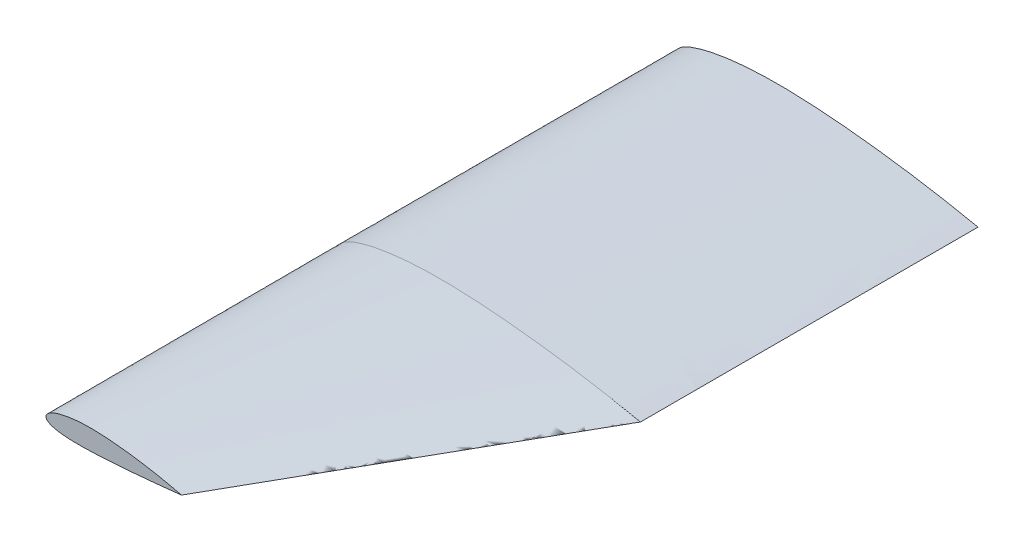
SolidWorks part; units mm, degrees
ref_plane "Front Plane" through (0, 0, 0) normal (0, 0, 1) x (1, 0, 0)
ref_plane "Top Plane" through (0, 0, 0) normal (0, 1, 0) x (1, 0, 0)
ref_plane "Right Plane" through (0, 0, 0) normal (1, 0, 0) x (0, 0, -1)
curve "Airfoil_curve"
  spline degree 3 poles (411.7804, -0.0098, 0) (412.0545, -0.0037, 0) (411.7837, 0.039, 0) (411.5616, 0.0985, 0) (411.0133, 0.2083, 0) (410.3302, 0.3565, 0) (409.4198, 0.5493, 0) (408.3206, 0.7814, 0) (407.02, 1.0557, 0) (405.5236, 1.3688, 0) (403.8317, 1.7216, 0) (401.9459, 2.1114, 0) (399.8683, 2.5387, 0) (397.6004, 3.0012, 0) (395.1447, 3.4977, 0) (392.5032, 4.0277, 0) (389.6784, 4.588, 0) (386.6731, 5.1782, 0) (383.49, 5.7963, 0) (380.1322, 6.4415, 0) (376.6026, 7.1106, 0) (372.9048, 7.8026, 0) (369.0422, 8.5155, 0) (365.0185, 9.2477, 0) (360.8375, 9.9974, 0) (356.5033, 10.7622, 0) (352.0198, 11.5401, 0) (347.3916, 12.3302, 0) (342.6227, 13.1295, 0) (337.7182, 13.9369, 0) (332.6823, 14.7493, 0) (327.5203, 15.5662, 0) (322.2368, 16.3844, 0) (316.8373, 17.2029, 0) (311.3268, 18.0191, 0) (305.7109, 18.8317, 0) (299.9947, 19.6388, 0) (294.184, 20.4376, 0) (288.2845, 21.2273, 0) (282.3019, 22.0053, 0) (276.2423, 22.7702, 0) (270.1111, 23.5198, 0) (263.9148, 24.2525, 0) (257.6594, 24.9668, 0) (251.3511, 25.6606, 0) (244.9963, 26.3314, 0) (238.6009, 26.9786, 0) (232.1717, 27.6004, 0) (225.7146, 28.1938, 0) (219.2366, 28.7588, 0) (212.7437, 29.2926, 0) (206.2427, 29.7945, 0) (199.7399, 30.2623, 0) (193.242, 30.6937, 0) (186.7555, 31.0897, 0) (180.2868, 31.4464, 0) (173.8427, 31.7639, 0) (167.4194, 32.0406, 0) (161.0164, 32.2752, 0) (154.6398, 32.4509, 0) (148.3063, 32.5705, 0) (142.0295, 32.6318, 0) (135.816, 32.6344, 0) (129.6725, 32.5795, 0) (123.6053, 32.4649, 0) (117.6211, 32.2936, 0) (111.726, 32.063, 0) (105.9265, 31.7758, 0) (100.2285, 31.4313, 0) (94.6381, 31.0317, 0) (89.1611, 30.5765, 0) (83.8035, 30.0681, 0) (78.5708, 29.5072, 0) (73.4685, 28.8959, 0) (68.5021, 28.2349, 0) (63.6766, 27.5273, 0) (58.9972, 26.7742, 0) (54.4684, 25.9781, 0) (50.0951, 25.1405, 0) (45.8815, 24.2652, 0) (41.8321, 23.353, 0) (37.9509, 22.4065, 0) (34.2415, 21.4297, 0) (30.7079, 20.4234, 0) (27.3533, 19.3907, 0) (24.1807, 18.3351, 0) (21.1936, 17.2578, 0) (18.3943, 16.1622, 0) (15.7854, 15.0508, 0) (13.3694, 13.9255, 0) (11.1484, 12.7884, 0) (9.1237, 11.6427, 0) (7.2972, 10.4899, 0) (5.6707, 9.3311, 0) (4.2438, 8.1697, 0) (3.0192, 7.0045, 0) (1.9965, 5.8381, 0) (1.1764, 4.6704, 0) (0.5611, 3.501, 0) (0.1532, 2.33, 0) (-0.0466, 1.1593, 0) (-0.034, -0.0035, 0) (0.184, -1.1455, 0) (0.6105, -2.2536, 0) (1.24, -3.3206, 0) (2.0693, -4.3466, 0) (3.0957, -5.3321, 0) (4.3175, -6.278, 0) (5.7326, -7.1853, 0) (7.3399, -8.0547, 0) (9.1377, -8.8859, 0) (11.1242, -9.6788, 0) (13.2976, -10.4332, 0) (15.6554, -11.149, 0) (18.1954, -11.8258, 0) (20.9147, -12.4638, 0) (23.8109, -13.0622, 0) (26.8805, -13.6221, 0) (30.121, -14.1417, 0) (33.5286, -14.6226, 0) (37.1002, -15.0646, 0) (40.8321, -15.467, 0) (44.7208, -15.8301, 0) (48.7622, -16.1562, 0) (52.9526, -16.4427, 0) (57.288, -16.693, 0) (61.7642, -16.9058, 0) (66.3771, -17.083, 0) (71.122, -17.2254, 0) (75.9947, -17.3326, 0) (80.9908, -17.4083, 0) (86.1054, -17.4505, 0) (91.334, -17.4635, 0) (96.6716, -17.4463, 0) (102.1135, -17.4017, 0) (107.6548, -17.3315, 0) (113.2902, -17.2356, 0) (119.0147, -17.1175, 0) (124.8229, -16.978, 0) (130.7098, -16.8184, 0) (136.6699, -16.6418, 0) (142.6978, -16.4497, 0) (148.7878, -16.2427, 0) (154.9346, -16.0246, 0) (161.1392, -15.7942, 0) (167.4062, -15.558, 0) (173.7288, -15.3015, 0) (180.0942, -15.0268, 0) (186.486, -14.734, 0) (192.8982, -14.4257, 0) (199.3245, -14.1034, 0) (205.7589, -13.7685, 0) (212.1948, -13.4218, 0) (218.6262, -13.0656, 0) (225.0467, -12.6998, 0) (231.4503, -12.3277, 0) (237.8305, -11.9483, 0) (244.1811, -11.565, 0) (250.4959, -11.1774, 0) (256.7687, -10.7861, 0) (262.9933, -10.3943, 0) (269.1636, -10.0009, 0) (275.2735, -9.6068, 0) (281.317, -9.2146, 0) (287.2881, -8.823, 0) (293.1808, -8.4343, 0) (298.9893, -8.0484, 0) (304.7077, -7.6657, 0) (310.3305, -7.2871, 0) (315.852, -6.9136, 0) (321.2667, -6.5455, 0) (326.569, -6.1826, 0) (331.7537, -5.8258, 0) (336.8156, -5.4765, 0) (341.7494, -5.133, 0) (346.5503, -4.7981, 0) (351.2134, -4.4704, 0) (355.7341, -4.152, 0) (360.1075, -3.8411, 0) (364.3295, -3.5402, 0) (368.3955, -3.2486, 0) (372.3014, -2.967, 0) (376.0433, -2.6953, 0) (379.6173, -2.4354, 0) (383.0197, -2.1855, 0) (386.247, -1.948, 0) (389.296, -1.7225, 0) (392.1633, -1.5084, 0) (394.8463, -1.308, 0) (397.3419, -1.1207, 0) (399.6476, -0.9463, 0) (401.7609, -0.7863, 0) (403.6795, -0.6398, 0) (405.4018, -0.5087, 0) (406.9253, -0.3915, 0) (408.2502, -0.2899, 0) (409.3701, -0.2034, 0) (410.298, -0.1323, 0) (410.9947, -0.0762, 0) (411.5525, -0.0391, 0) (411.7804, -0.0098, 0) (412.0545, -0.0037, 0) (411.7837, 0.039, 0) knots -0.0011 -0.000489 -0.000122 0 0.000122 0.000489 0.001101 0.001956 0.003053 0.004392 0.005972 0.007791 0.009846 0.012136 0.014659 0.017411 0.020391 0.023594 0.02702 0.030662 0.034518 0.038584 0.042857 0.04733 0.052001 0.056865 0.061917 0.067151 0.072562 0.078146 0.083896 0.089808 0.095874 0.102089 0.108447 0.114942 0.121567 0.128315 0.13518 0.142156 0.149234 0.156409 0.163672 0.171018 0.178438 0.185926 0.193473 0.201072 0.208716 0.216398 0.224109 0.231843 0.23959 0.247345 0.255098 0.262842 0.27057 0.278275 0.285948 0.293582 0.301205 0.308799 0.316332 0.323797 0.331187 0.338493 0.345709 0.352829 0.359844 0.36675 0.373538 0.380203 0.386738 0.393139 0.399397 0.405507 0.411466 0.417265 0.422901 0.428369 0.433664 0.438782 0.443717 0.448468 0.453029 0.457397 0.461571 0.465546 0.469321 0.472895 0.476266 0.479434 0.482399 0.485163 0.487728 0.490098 0.492281 0.494284 0.49612 0.497805 0.499362 0.500818 0.502209 0.503576 0.504943 0.506334 0.507789 0.509344 0.511025 0.512853 0.514846 0.517014 0.519365 0.521906 0.524639 0.527568 0.530692 0.534013 0.537528 0.541238 0.54514 0.549232 0.553512 0.557975 0.562619 0.567441 0.572435 0.577599 0.582928 0.588418 0.594063 0.599859 0.605801 0.611883 0.618101 0.624448 0.63092 0.63751 0.644213 0.651022 0.657931 0.664934 0.672025 0.679197 0.686444 0.693758 0.701134 0.708588 0.716126 0.723702 0.731312 0.738946 0.746598 0.75426 0.761925 0.769585 0.777233 0.784861 0.792462 0.800028 0.807552 0.815027 0.822444 0.829797 0.837078 0.84428 0.851396 0.85842 0.865343 0.872158 0.87886 0.885442 0.891896 0.898216 0.904397 0.910431 0.916313 0.922036 0.927595 0.932985 0.938199 0.943233 0.948081 0.952738 0.9572 0.961461 0.965519 0.969367 0.973003 0.976422 0.979622 0.982599 0.985348 0.987869 0.990157 0.992211 0.994029 0.995608 0.996947 0.998045 0.9989 0.999511 0.999878 1 1.000122 1.000489 1.001101 periodic
ref_plane "Panel break" through (0, 0, 461) normal (0, 0, 1) x (1, 0, 0)
sketch "panel 1 root " plane through (0, 0, 0) normal (0, 0, 1) x (1, 0, 0)
  spline S0 degree 3 poles (411.7804, -0.0098) (412.0545, -0.0037) (411.7837, 0.039) (411.5616, 0.0985) (411.0133, 0.2083) (410.3302, 0.3565) (409.4198, 0.5493) (408.3206, 0.7814) (407.02, 1.0557) (405.5236, 1.3688) (403.8317, 1.7216) (401.9459, 2.1114) (399.8683, 2.5387) (397.6004, 3.0012) (395.1447, 3.4977) (392.5032, 4.0277) (389.6784, 4.588) (386.6731, 5.1782) (383.49, 5.7963) (380.1322, 6.4415) (376.6026, 7.1106) (372.9048, 7.8026) (369.0422, 8.5155) (365.0185, 9.2477) (360.8375, 9.9974) (356.5033, 10.7622) (352.0198, 11.5401) (347.3916, 12.3302) (342.6227, 13.1295) (337.7182, 13.9369) (332.6823, 14.7493) (327.5203, 15.5662) (322.2368, 16.3844) (316.8373, 17.2029) (311.3268, 18.0191) (305.7109, 18.8317) (299.9947, 19.6388) (294.184, 20.4376) (288.2845, 21.2273) (282.3019, 22.0053) (276.2423, 22.7702) (270.1111, 23.5198) (263.9148, 24.2525) (257.6594, 24.9668) (251.3511, 25.6606) (244.9963, 26.3314) (238.6009, 26.9786) (232.1717, 27.6004) (225.7146, 28.1938) (219.2366, 28.7588) (212.7437, 29.2926) (206.2427, 29.7945) (199.7399, 30.2623) (193.242, 30.6937) (186.7555, 31.0897) (180.2868, 31.4464) (173.8427, 31.7639) (167.4194, 32.0406) (161.0164, 32.2752) (154.6398, 32.4509) (148.3063, 32.5705) (142.0295, 32.6318) (135.816, 32.6344) (129.6725, 32.5795) (123.6053, 32.4649) (117.6211, 32.2936) (111.726, 32.063) (105.9265, 31.7758) (100.2285, 31.4313) (94.6381, 31.0317) (89.1611, 30.5765) (83.8035, 30.0681) (78.5708, 29.5072) (73.4685, 28.8959) (68.5021, 28.2349) (63.6766, 27.5273) (58.9972, 26.7742) (54.4684, 25.9781) (50.0951, 25.1405) (45.8815, 24.2652) (41.8321, 23.353) (37.9509, 22.4065) (34.2415, 21.4297) (30.7079, 20.4234) (27.3533, 19.3907) (24.1807, 18.3351) (21.1936, 17.2578) (18.3943, 16.1622) (15.7854, 15.0508) (13.3694, 13.9255) (11.1484, 12.7884) (9.1237, 11.6427) (7.2972, 10.4899) (5.6707, 9.3311) (4.2438, 8.1697) (3.0192, 7.0045) (1.9965, 5.8381) (1.1764, 4.6704) (0.5611, 3.501) (0.1532, 2.33) (-0.0466, 1.1593) (-0.034, -0.0035) (0.184, -1.1455) (0.6105, -2.2536) (1.24, -3.3206) (2.0693, -4.3466) (3.0957, -5.3321) (4.3175, -6.278) (5.7326, -7.1853) (7.3399, -8.0547) (9.1377, -8.8859) (11.1242, -9.6788) (13.2976, -10.4332) (15.6554, -11.149) (18.1954, -11.8258) (20.9147, -12.4638) (23.8109, -13.0622) (26.8805, -13.6221) (30.121, -14.1417) (33.5286, -14.6226) (37.1002, -15.0646) (40.8321, -15.467) (44.7208, -15.8301) (48.7622, -16.1562) (52.9526, -16.4427) (57.288, -16.693) (61.7642, -16.9058) (66.3771, -17.083) (71.122, -17.2254) (75.9947, -17.3326) (80.9908, -17.4083) (86.1054, -17.4505) (91.334, -17.4635) (96.6716, -17.4463) (102.1135, -17.4017) (107.6548, -17.3315) (113.2902, -17.2356) (119.0147, -17.1175) (124.8229, -16.978) (130.7098, -16.8184) (136.6699, -16.6418) (142.6978, -16.4497) (148.7878, -16.2427) (154.9346, -16.0246) (161.1392, -15.7942) (167.4062, -15.558) (173.7288, -15.3015) (180.0942, -15.0268) (186.486, -14.734) (192.8982, -14.4257) (199.3245, -14.1034) (205.7589, -13.7685) (212.1948, -13.4218) (218.6262, -13.0656) (225.0467, -12.6998) (231.4503, -12.3277) (237.8305, -11.9483) (244.1811, -11.565) (250.4959, -11.1774) (256.7687, -10.7861) (262.9933, -10.3943) (269.1636, -10.0009) (275.2735, -9.6068) (281.317, -9.2146) (287.2881, -8.823) (293.1808, -8.4343) (298.9893, -8.0484) (304.7077, -7.6657) (310.3305, -7.2871) (315.852, -6.9136) (321.2667, -6.5455) (326.569, -6.1826) (331.7537, -5.8258) (336.8156, -5.4765) (341.7494, -5.133) (346.5503, -4.7981) (351.2134, -4.4704) (355.7341, -4.152) (360.1075, -3.8411) (364.3295, -3.5402) (368.3955, -3.2486) (372.3014, -2.967) (376.0433, -2.6953) (379.6173, -2.4354) (383.0197, -2.1855) (386.247, -1.948) (389.296, -1.7225) (392.1633, -1.5084) (394.8463, -1.308) (397.3419, -1.1207) (399.6476, -0.9463) (401.7609, -0.7863) (403.6795, -0.6398) (405.4018, -0.5087) (406.9253, -0.3915) (408.2502, -0.2899) (409.3701, -0.2034) (410.298, -0.1323) (410.9947, -0.0762) (411.5525, -0.0391) (411.7804, -0.0098) (412.0545, -0.0037) (411.7837, 0.039) knots -0.0011 -0.000489 -0.000122 0 0.000122 0.000489 0.001101 0.001956 0.003053 0.004392 0.005972 0.007791 0.009846 0.012136 0.014659 0.017411 0.020391 0.023594 0.02702 0.030662 0.034518 0.038584 0.042857 0.04733 0.052001 0.056865 0.061917 0.067151 0.072562 0.078146 0.083896 0.089808 0.095874 0.102089 0.108447 0.114942 0.121567 0.128315 0.13518 0.142156 0.149234 0.156409 0.163672 0.171018 0.178438 0.185926 0.193473 0.201072 0.208716 0.216398 0.224109 0.231843 0.23959 0.247345 0.255098 0.262842 0.27057 0.278275 0.285948 0.293582 0.301205 0.308799 0.316332 0.323797 0.331187 0.338493 0.345709 0.352829 0.359844 0.36675 0.373538 0.380203 0.386738 0.393139 0.399397 0.405507 0.411466 0.417265 0.422901 0.428369 0.433664 0.438782 0.443717 0.448468 0.453029 0.457397 0.461571 0.465546 0.469321 0.472895 0.476266 0.479434 0.482399 0.485163 0.487728 0.490098 0.492281 0.494284 0.49612 0.497805 0.499362 0.500818 0.502209 0.503576 0.504943 0.506334 0.507789 0.509344 0.511025 0.512853 0.514846 0.517014 0.519365 0.521906 0.524639 0.527568 0.530692 0.534013 0.537528 0.541238 0.54514 0.549232 0.553512 0.557975 0.562619 0.567441 0.572435 0.577599 0.582928 0.588418 0.594063 0.599859 0.605801 0.611883 0.618101 0.624448 0.63092 0.63751 0.644213 0.651022 0.657931 0.664934 0.672025 0.679197 0.686444 0.693758 0.701134 0.708588 0.716126 0.723702 0.731312 0.738946 0.746598 0.75426 0.761925 0.769585 0.777233 0.784861 0.792462 0.800028 0.807552 0.815027 0.822444 0.829797 0.837078 0.84428 0.851396 0.85842 0.865343 0.872158 0.87886 0.885442 0.891896 0.898216 0.904397 0.910431 0.916313 0.922036 0.927595 0.932985 0.938199 0.943233 0.948081 0.952738 0.9572 0.961461 0.965519 0.969367 0.973003 0.976422 0.979622 0.982599 0.985348 0.987869 0.990157 0.992211 0.994029 0.995608 0.996947 0.998045 0.9989 0.999511 0.999878 1 1.000122 1.000489 1.001101 only from (412, 0) to (412, 0) construction
  spline S1 degree 3 poles (411.7804, -0.0098) (412.0545, -0.0037) (411.7837, 0.039) (411.5616, 0.0985) (411.0133, 0.2083) (410.3302, 0.3565) (409.4198, 0.5493) (408.3206, 0.7814) (407.02, 1.0557) (405.5236, 1.3688) (403.8317, 1.7216) (401.9459, 2.1114) (399.8683, 2.5387) (397.6004, 3.0012) (395.1447, 3.4977) (392.5032, 4.0277) (389.6784, 4.588) (386.6731, 5.1782) (383.49, 5.7963) (380.1322, 6.4415) (376.6026, 7.1106) (372.9048, 7.8026) (369.0422, 8.5155) (365.0185, 9.2477) (360.8375, 9.9974) (356.5033, 10.7622) (352.0198, 11.5401) (347.3916, 12.3302) (342.6227, 13.1295) (337.7182, 13.9369) (332.6823, 14.7493) (327.5203, 15.5662) (322.2368, 16.3844) (316.8373, 17.2029) (311.3268, 18.0191) (305.7109, 18.8317) (299.9947, 19.6388) (294.184, 20.4376) (288.2845, 21.2273) (282.3019, 22.0053) (276.2423, 22.7702) (270.1111, 23.5198) (263.9148, 24.2525) (257.6594, 24.9668) (251.3511, 25.6606) (244.9963, 26.3314) (238.6009, 26.9786) (232.1717, 27.6004) (225.7146, 28.1938) (219.2366, 28.7588) (212.7437, 29.2926) (206.2427, 29.7945) (199.7399, 30.2623) (193.242, 30.6937) (186.7555, 31.0897) (180.2868, 31.4464) (173.8427, 31.7639) (167.4194, 32.0406) (161.0164, 32.2752) (154.6398, 32.4509) (148.3063, 32.5705) (142.0295, 32.6318) (135.816, 32.6344) (129.6725, 32.5795) (123.6053, 32.4649) (117.6211, 32.2936) (111.726, 32.063) (105.9265, 31.7758) (100.2285, 31.4313) (94.6381, 31.0317) (89.1611, 30.5765) (83.8035, 30.0681) (78.5708, 29.5072) (73.4685, 28.8959) (68.5021, 28.2349) (63.6766, 27.5273) (58.9972, 26.7742) (54.4684, 25.9781) (50.0951, 25.1405) (45.8815, 24.2652) (41.8321, 23.353) (37.9509, 22.4065) (34.2415, 21.4297) (30.7079, 20.4234) (27.3533, 19.3907) (24.1807, 18.3351) (21.1936, 17.2578) (18.3943, 16.1622) (15.7854, 15.0508) (13.3694, 13.9255) (11.1484, 12.7884) (9.1237, 11.6427) (7.2972, 10.4899) (5.6707, 9.3311) (4.2438, 8.1697) (3.0192, 7.0045) (1.9965, 5.8381) (1.1764, 4.6704) (0.5611, 3.501) (0.1532, 2.33) (-0.0466, 1.1593) (-0.034, -0.0035) (0.184, -1.1455) (0.6105, -2.2536) (1.24, -3.3206) (2.0693, -4.3466) (3.0957, -5.3321) (4.3175, -6.278) (5.7326, -7.1853) (7.3399, -8.0547) (9.1377, -8.8859) (11.1242, -9.6788) (13.2976, -10.4332) (15.6554, -11.149) (18.1954, -11.8258) (20.9147, -12.4638) (23.8109, -13.0622) (26.8805, -13.6221) (30.121, -14.1417) (33.5286, -14.6226) (37.1002, -15.0646) (40.8321, -15.467) (44.7208, -15.8301) (48.7622, -16.1562) (52.9526, -16.4427) (57.288, -16.693) (61.7642, -16.9058) (66.3771, -17.083) (71.122, -17.2254) (75.9947, -17.3326) (80.9908, -17.4083) (86.1054, -17.4505) (91.334, -17.4635) (96.6716, -17.4463) (102.1135, -17.4017) (107.6548, -17.3315) (113.2902, -17.2356) (119.0147, -17.1175) (124.8229, -16.978) (130.7098, -16.8184) (136.6699, -16.6418) (142.6978, -16.4497) (148.7878, -16.2427) (154.9346, -16.0246) (161.1392, -15.7942) (167.4062, -15.558) (173.7288, -15.3015) (180.0942, -15.0268) (186.486, -14.734) (192.8982, -14.4257) (199.3245, -14.1034) (205.7589, -13.7685) (212.1948, -13.4218) (218.6262, -13.0656) (225.0467, -12.6998) (231.4503, -12.3277) (237.8305, -11.9483) (244.1811, -11.565) (250.4959, -11.1774) (256.7687, -10.7861) (262.9933, -10.3943) (269.1636, -10.0009) (275.2735, -9.6068) (281.317, -9.2146) (287.2881, -8.823) (293.1808, -8.4343) (298.9893, -8.0484) (304.7077, -7.6657) (310.3305, -7.2871) (315.852, -6.9136) (321.2667, -6.5455) (326.569, -6.1826) (331.7537, -5.8258) (336.8156, -5.4765) (341.7494, -5.133) (346.5503, -4.7981) (351.2134, -4.4704) (355.7341, -4.152) (360.1075, -3.8411) (364.3295, -3.5402) (368.3955, -3.2486) (372.3014, -2.967) (376.0433, -2.6953) (379.6173, -2.4354) (383.0197, -2.1855) (386.247, -1.948) (389.296, -1.7225) (392.1633, -1.5084) (394.8463, -1.308) (397.3419, -1.1207) (399.6476, -0.9463) (401.7609, -0.7863) (403.6795, -0.6398) (405.4018, -0.5087) (406.9253, -0.3915) (408.2502, -0.2899) (409.3701, -0.2034) (410.298, -0.1323) (410.9947, -0.0762) (411.5525, -0.0391) (411.7804, -0.0098) (412.0545, -0.0037) (411.7837, 0.039) knots -0.0011 -0.000489 -0.000122 0 0.000122 0.000489 0.001101 0.001956 0.003053 0.004392 0.005972 0.007791 0.009846 0.012136 0.014659 0.017411 0.020391 0.023594 0.02702 0.030662 0.034518 0.038584 0.042857 0.04733 0.052001 0.056865 0.061917 0.067151 0.072562 0.078146 0.083896 0.089808 0.095874 0.102089 0.108447 0.114942 0.121567 0.128315 0.13518 0.142156 0.149234 0.156409 0.163672 0.171018 0.178438 0.185926 0.193473 0.201072 0.208716 0.216398 0.224109 0.231843 0.23959 0.247345 0.255098 0.262842 0.27057 0.278275 0.285948 0.293582 0.301205 0.308799 0.316332 0.323797 0.331187 0.338493 0.345709 0.352829 0.359844 0.36675 0.373538 0.380203 0.386738 0.393139 0.399397 0.405507 0.411466 0.417265 0.422901 0.428369 0.433664 0.438782 0.443717 0.448468 0.453029 0.457397 0.461571 0.465546 0.469321 0.472895 0.476266 0.479434 0.482399 0.485163 0.487728 0.490098 0.492281 0.494284 0.49612 0.497805 0.499362 0.500818 0.502209 0.503576 0.504943 0.506334 0.507789 0.509344 0.511025 0.512853 0.514846 0.517014 0.519365 0.521906 0.524639 0.527568 0.530692 0.534013 0.537528 0.541238 0.54514 0.549232 0.553512 0.557975 0.562619 0.567441 0.572435 0.577599 0.582928 0.588418 0.594063 0.599859 0.605801 0.611883 0.618101 0.624448 0.63092 0.63751 0.644213 0.651022 0.657931 0.664934 0.672025 0.679197 0.686444 0.693758 0.701134 0.708588 0.716126 0.723702 0.731312 0.738946 0.746598 0.75426 0.761925 0.769585 0.777233 0.784861 0.792462 0.800028 0.807552 0.815027 0.822444 0.829797 0.837078 0.84428 0.851396 0.85842 0.865343 0.872158 0.87886 0.885442 0.891896 0.898216 0.904397 0.910431 0.916313 0.922036 0.927595 0.932985 0.938199 0.943233 0.948081 0.952738 0.9572 0.961461 0.965519 0.969367 0.973003 0.976422 0.979622 0.982599 0.985348 0.987869 0.990157 0.992211 0.994029 0.995608 0.996947 0.998045 0.9989 0.999511 0.999878 1 1.000122 1.000489 1.001101 only from (412, 0) to (412, 0)
sketch "panel 2 root " plane through (0, 0, 461) normal (0, 0, 1) x (1, 0, 0)
  spline S0 degree 3 poles (411.7804, -0.0098) (412.0545, -0.0037) (411.7837, 0.039) (411.5616, 0.0985) (411.0133, 0.2083) (410.3302, 0.3565) (409.4198, 0.5493) (408.3206, 0.7814) (407.02, 1.0557) (405.5236, 1.3688) (403.8317, 1.7216) (401.9459, 2.1114) (399.8683, 2.5387) (397.6004, 3.0012) (395.1447, 3.4977) (392.5032, 4.0277) (389.6784, 4.588) (386.6731, 5.1782) (383.49, 5.7963) (380.1322, 6.4415) (376.6026, 7.1106) (372.9048, 7.8026) (369.0422, 8.5155) (365.0185, 9.2477) (360.8375, 9.9974) (356.5033, 10.7622) (352.0198, 11.5401) (347.3916, 12.3302) (342.6227, 13.1295) (337.7182, 13.9369) (332.6823, 14.7493) (327.5203, 15.5662) (322.2368, 16.3844) (316.8373, 17.2029) (311.3268, 18.0191) (305.7109, 18.8317) (299.9947, 19.6388) (294.184, 20.4376) (288.2845, 21.2273) (282.3019, 22.0053) (276.2423, 22.7702) (270.1111, 23.5198) (263.9148, 24.2525) (257.6594, 24.9668) (251.3511, 25.6606) (244.9963, 26.3314) (238.6009, 26.9786) (232.1717, 27.6004) (225.7146, 28.1938) (219.2366, 28.7588) (212.7437, 29.2926) (206.2427, 29.7945) (199.7399, 30.2623) (193.242, 30.6937) (186.7555, 31.0897) (180.2868, 31.4464) (173.8427, 31.7639) (167.4194, 32.0406) (161.0164, 32.2752) (154.6398, 32.4509) (148.3063, 32.5705) (142.0295, 32.6318) (135.816, 32.6344) (129.6725, 32.5795) (123.6053, 32.4649) (117.6211, 32.2936) (111.726, 32.063) (105.9265, 31.7758) (100.2285, 31.4313) (94.6381, 31.0317) (89.1611, 30.5765) (83.8035, 30.0681) (78.5708, 29.5072) (73.4685, 28.8959) (68.5021, 28.2349) (63.6766, 27.5273) (58.9972, 26.7742) (54.4684, 25.9781) (50.0951, 25.1405) (45.8815, 24.2652) (41.8321, 23.353) (37.9509, 22.4065) (34.2415, 21.4297) (30.7079, 20.4234) (27.3533, 19.3907) (24.1807, 18.3351) (21.1936, 17.2578) (18.3943, 16.1622) (15.7854, 15.0508) (13.3694, 13.9255) (11.1484, 12.7884) (9.1237, 11.6427) (7.2972, 10.4899) (5.6707, 9.3311) (4.2438, 8.1697) (3.0192, 7.0045) (1.9965, 5.8381) (1.1764, 4.6704) (0.5611, 3.501) (0.1532, 2.33) (-0.0466, 1.1593) (-0.034, -0.0035) (0.184, -1.1455) (0.6105, -2.2536) (1.24, -3.3206) (2.0693, -4.3466) (3.0957, -5.3321) (4.3175, -6.278) (5.7326, -7.1853) (7.3399, -8.0547) (9.1377, -8.8859) (11.1242, -9.6788) (13.2976, -10.4332) (15.6554, -11.149) (18.1954, -11.8258) (20.9147, -12.4638) (23.8109, -13.0622) (26.8805, -13.6221) (30.121, -14.1417) (33.5286, -14.6226) (37.1002, -15.0646) (40.8321, -15.467) (44.7208, -15.8301) (48.7622, -16.1562) (52.9526, -16.4427) (57.288, -16.693) (61.7642, -16.9058) (66.3771, -17.083) (71.122, -17.2254) (75.9947, -17.3326) (80.9908, -17.4083) (86.1054, -17.4505) (91.334, -17.4635) (96.6716, -17.4463) (102.1135, -17.4017) (107.6548, -17.3315) (113.2902, -17.2356) (119.0147, -17.1175) (124.8229, -16.978) (130.7098, -16.8184) (136.6699, -16.6418) (142.6978, -16.4497) (148.7878, -16.2427) (154.9346, -16.0246) (161.1392, -15.7942) (167.4062, -15.558) (173.7288, -15.3015) (180.0942, -15.0268) (186.486, -14.734) (192.8982, -14.4257) (199.3245, -14.1034) (205.7589, -13.7685) (212.1948, -13.4218) (218.6262, -13.0656) (225.0467, -12.6998) (231.4503, -12.3277) (237.8305, -11.9483) (244.1811, -11.565) (250.4959, -11.1774) (256.7687, -10.7861) (262.9933, -10.3943) (269.1636, -10.0009) (275.2735, -9.6068) (281.317, -9.2146) (287.2881, -8.823) (293.1808, -8.4343) (298.9893, -8.0484) (304.7077, -7.6657) (310.3305, -7.2871) (315.852, -6.9136) (321.2667, -6.5455) (326.569, -6.1826) (331.7537, -5.8258) (336.8156, -5.4765) (341.7494, -5.133) (346.5503, -4.7981) (351.2134, -4.4704) (355.7341, -4.152) (360.1075, -3.8411) (364.3295, -3.5402) (368.3955, -3.2486) (372.3014, -2.967) (376.0433, -2.6953) (379.6173, -2.4354) (383.0197, -2.1855) (386.247, -1.948) (389.296, -1.7225) (392.1633, -1.5084) (394.8463, -1.308) (397.3419, -1.1207) (399.6476, -0.9463) (401.7609, -0.7863) (403.6795, -0.6398) (405.4018, -0.5087) (406.9253, -0.3915) (408.2502, -0.2899) (409.3701, -0.2034) (410.298, -0.1323) (410.9947, -0.0762) (411.5525, -0.0391) (411.7804, -0.0098) (412.0545, -0.0037) (411.7837, 0.039) knots -0.0011 -0.000489 -0.000122 0 0.000122 0.000489 0.001101 0.001956 0.003053 0.004392 0.005972 0.007791 0.009846 0.012136 0.014659 0.017411 0.020391 0.023594 0.02702 0.030662 0.034518 0.038584 0.042857 0.04733 0.052001 0.056865 0.061917 0.067151 0.072562 0.078146 0.083896 0.089808 0.095874 0.102089 0.108447 0.114942 0.121567 0.128315 0.13518 0.142156 0.149234 0.156409 0.163672 0.171018 0.178438 0.185926 0.193473 0.201072 0.208716 0.216398 0.224109 0.231843 0.23959 0.247345 0.255098 0.262842 0.27057 0.278275 0.285948 0.293582 0.301205 0.308799 0.316332 0.323797 0.331187 0.338493 0.345709 0.352829 0.359844 0.36675 0.373538 0.380203 0.386738 0.393139 0.399397 0.405507 0.411466 0.417265 0.422901 0.428369 0.433664 0.438782 0.443717 0.448468 0.453029 0.457397 0.461571 0.465546 0.469321 0.472895 0.476266 0.479434 0.482399 0.485163 0.487728 0.490098 0.492281 0.494284 0.49612 0.497805 0.499362 0.500818 0.502209 0.503576 0.504943 0.506334 0.507789 0.509344 0.511025 0.512853 0.514846 0.517014 0.519365 0.521906 0.524639 0.527568 0.530692 0.534013 0.537528 0.541238 0.54514 0.549232 0.553512 0.557975 0.562619 0.567441 0.572435 0.577599 0.582928 0.588418 0.594063 0.599859 0.605801 0.611883 0.618101 0.624448 0.63092 0.63751 0.644213 0.651022 0.657931 0.664934 0.672025 0.679197 0.686444 0.693758 0.701134 0.708588 0.716126 0.723702 0.731312 0.738946 0.746598 0.75426 0.761925 0.769585 0.777233 0.784861 0.792462 0.800028 0.807552 0.815027 0.822444 0.829797 0.837078 0.84428 0.851396 0.85842 0.865343 0.872158 0.87886 0.885442 0.891896 0.898216 0.904397 0.910431 0.916313 0.922036 0.927595 0.932985 0.938199 0.943233 0.948081 0.952738 0.9572 0.961461 0.965519 0.969367 0.973003 0.976422 0.979622 0.982599 0.985348 0.987869 0.990157 0.992211 0.994029 0.995608 0.996947 0.998045 0.9989 0.999511 0.999878 1 1.000122 1.000489 1.001101 only from (412, 0) to (412, 0) construction
  spline S1 degree 3 poles (411.7804, -0.0098) (412.0545, -0.0037) (411.7837, 0.039) (411.5616, 0.0985) (411.0133, 0.2083) (410.3302, 0.3565) (409.4198, 0.5493) (408.3206, 0.7814) (407.02, 1.0557) (405.5236, 1.3688) (403.8317, 1.7216) (401.9459, 2.1114) (399.8683, 2.5387) (397.6004, 3.0012) (395.1447, 3.4977) (392.5032, 4.0277) (389.6784, 4.588) (386.6731, 5.1782) (383.49, 5.7963) (380.1322, 6.4415) (376.6026, 7.1106) (372.9048, 7.8026) (369.0422, 8.5155) (365.0185, 9.2477) (360.8375, 9.9974) (356.5033, 10.7622) (352.0198, 11.5401) (347.3916, 12.3302) (342.6227, 13.1295) (337.7182, 13.9369) (332.6823, 14.7493) (327.5203, 15.5662) (322.2368, 16.3844) (316.8373, 17.2029) (311.3268, 18.0191) (305.7109, 18.8317) (299.9947, 19.6388) (294.184, 20.4376) (288.2845, 21.2273) (282.3019, 22.0053) (276.2423, 22.7702) (270.1111, 23.5198) (263.9148, 24.2525) (257.6594, 24.9668) (251.3511, 25.6606) (244.9963, 26.3314) (238.6009, 26.9786) (232.1717, 27.6004) (225.7146, 28.1938) (219.2366, 28.7588) (212.7437, 29.2926) (206.2427, 29.7945) (199.7399, 30.2623) (193.242, 30.6937) (186.7555, 31.0897) (180.2868, 31.4464) (173.8427, 31.7639) (167.4194, 32.0406) (161.0164, 32.2752) (154.6398, 32.4509) (148.3063, 32.5705) (142.0295, 32.6318) (135.816, 32.6344) (129.6725, 32.5795) (123.6053, 32.4649) (117.6211, 32.2936) (111.726, 32.063) (105.9265, 31.7758) (100.2285, 31.4313) (94.6381, 31.0317) (89.1611, 30.5765) (83.8035, 30.0681) (78.5708, 29.5072) (73.4685, 28.8959) (68.5021, 28.2349) (63.6766, 27.5273) (58.9972, 26.7742) (54.4684, 25.9781) (50.0951, 25.1405) (45.8815, 24.2652) (41.8321, 23.353) (37.9509, 22.4065) (34.2415, 21.4297) (30.7079, 20.4234) (27.3533, 19.3907) (24.1807, 18.3351) (21.1936, 17.2578) (18.3943, 16.1622) (15.7854, 15.0508) (13.3694, 13.9255) (11.1484, 12.7884) (9.1237, 11.6427) (7.2972, 10.4899) (5.6707, 9.3311) (4.2438, 8.1697) (3.0192, 7.0045) (1.9965, 5.8381) (1.1764, 4.6704) (0.5611, 3.501) (0.1532, 2.33) (-0.0466, 1.1593) (-0.034, -0.0035) (0.184, -1.1455) (0.6105, -2.2536) (1.24, -3.3206) (2.0693, -4.3466) (3.0957, -5.3321) (4.3175, -6.278) (5.7326, -7.1853) (7.3399, -8.0547) (9.1377, -8.8859) (11.1242, -9.6788) (13.2976, -10.4332) (15.6554, -11.149) (18.1954, -11.8258) (20.9147, -12.4638) (23.8109, -13.0622) (26.8805, -13.6221) (30.121, -14.1417) (33.5286, -14.6226) (37.1002, -15.0646) (40.8321, -15.467) (44.7208, -15.8301) (48.7622, -16.1562) (52.9526, -16.4427) (57.288, -16.693) (61.7642, -16.9058) (66.3771, -17.083) (71.122, -17.2254) (75.9947, -17.3326) (80.9908, -17.4083) (86.1054, -17.4505) (91.334, -17.4635) (96.6716, -17.4463) (102.1135, -17.4017) (107.6548, -17.3315) (113.2902, -17.2356) (119.0147, -17.1175) (124.8229, -16.978) (130.7098, -16.8184) (136.6699, -16.6418) (142.6978, -16.4497) (148.7878, -16.2427) (154.9346, -16.0246) (161.1392, -15.7942) (167.4062, -15.558) (173.7288, -15.3015) (180.0942, -15.0268) (186.486, -14.734) (192.8982, -14.4257) (199.3245, -14.1034) (205.7589, -13.7685) (212.1948, -13.4218) (218.6262, -13.0656) (225.0467, -12.6998) (231.4503, -12.3277) (237.8305, -11.9483) (244.1811, -11.565) (250.4959, -11.1774) (256.7687, -10.7861) (262.9933, -10.3943) (269.1636, -10.0009) (275.2735, -9.6068) (281.317, -9.2146) (287.2881, -8.823) (293.1808, -8.4343) (298.9893, -8.0484) (304.7077, -7.6657) (310.3305, -7.2871) (315.852, -6.9136) (321.2667, -6.5455) (326.569, -6.1826) (331.7537, -5.8258) (336.8156, -5.4765) (341.7494, -5.133) (346.5503, -4.7981) (351.2134, -4.4704) (355.7341, -4.152) (360.1075, -3.8411) (364.3295, -3.5402) (368.3955, -3.2486) (372.3014, -2.967) (376.0433, -2.6953) (379.6173, -2.4354) (383.0197, -2.1855) (386.247, -1.948) (389.296, -1.7225) (392.1633, -1.5084) (394.8463, -1.308) (397.3419, -1.1207) (399.6476, -0.9463) (401.7609, -0.7863) (403.6795, -0.6398) (405.4018, -0.5087) (406.9253, -0.3915) (408.2502, -0.2899) (409.3701, -0.2034) (410.298, -0.1323) (410.9947, -0.0762) (411.5525, -0.0391) (411.7804, -0.0098) (412.0545, -0.0037) (411.7837, 0.039) knots -0.0011 -0.000489 -0.000122 0 0.000122 0.000489 0.001101 0.001956 0.003053 0.004392 0.005972 0.007791 0.009846 0.012136 0.014659 0.017411 0.020391 0.023594 0.02702 0.030662 0.034518 0.038584 0.042857 0.04733 0.052001 0.056865 0.061917 0.067151 0.072562 0.078146 0.083896 0.089808 0.095874 0.102089 0.108447 0.114942 0.121567 0.128315 0.13518 0.142156 0.149234 0.156409 0.163672 0.171018 0.178438 0.185926 0.193473 0.201072 0.208716 0.216398 0.224109 0.231843 0.23959 0.247345 0.255098 0.262842 0.27057 0.278275 0.285948 0.293582 0.301205 0.308799 0.316332 0.323797 0.331187 0.338493 0.345709 0.352829 0.359844 0.36675 0.373538 0.380203 0.386738 0.393139 0.399397 0.405507 0.411466 0.417265 0.422901 0.428369 0.433664 0.438782 0.443717 0.448468 0.453029 0.457397 0.461571 0.465546 0.469321 0.472895 0.476266 0.479434 0.482399 0.485163 0.487728 0.490098 0.492281 0.494284 0.49612 0.497805 0.499362 0.500818 0.502209 0.503576 0.504943 0.506334 0.507789 0.509344 0.511025 0.512853 0.514846 0.517014 0.519365 0.521906 0.524639 0.527568 0.530692 0.534013 0.537528 0.541238 0.54514 0.549232 0.553512 0.557975 0.562619 0.567441 0.572435 0.577599 0.582928 0.588418 0.594063 0.599859 0.605801 0.611883 0.618101 0.624448 0.63092 0.63751 0.644213 0.651022 0.657931 0.664934 0.672025 0.679197 0.686444 0.693758 0.701134 0.708588 0.716126 0.723702 0.731312 0.738946 0.746598 0.75426 0.761925 0.769585 0.777233 0.784861 0.792462 0.800028 0.807552 0.815027 0.822444 0.829797 0.837078 0.84428 0.851396 0.85842 0.865343 0.872158 0.87886 0.885442 0.891896 0.898216 0.904397 0.910431 0.916313 0.922036 0.927595 0.932985 0.938199 0.943233 0.948081 0.952738 0.9572 0.961461 0.965519 0.969367 0.973003 0.976422 0.979622 0.982599 0.985348 0.987869 0.990157 0.992211 0.994029 0.995608 0.996947 0.998045 0.9989 0.999511 0.999878 1 1.000122 1.000489 1.001101 only from (412, 0) to (412, 0)
ref_plane "panel end " through (0, 0, 861) normal (0, 0, 1) x (1, 0, 0)
curve "airfoil tip curve"
  spline degree 3 poles (184.9011, -0.0072, 0) (185.0245, -0.0016, 0) (184.903, 0.0203, 0) (184.8036, 0.0517, 0) (184.5581, 0.1095, 0) (184.2522, 0.1877, 0) (183.8441, 0.2887, 0) (183.3518, 0.4112, 0) (182.769, 0.5551, 0) (182.0988, 0.7202, 0) (181.3407, 0.9053, 0) (180.4959, 1.1109, 0) (179.565, 1.3356, 0) (178.5487, 1.5789, 0) (177.4482, 1.8405, 0) (176.2644, 2.1191, 0) (174.9984, 2.4143, 0) (173.6514, 2.7252, 0) (172.2246, 3.0508, 0) (170.7194, 3.3906, 0) (169.137, 3.7432, 0) (167.4791, 4.1081, 0) (165.7471, 4.4841, 0) (163.9427, 4.8702, 0) (162.0677, 5.2659, 0) (160.1236, 5.6695, 0) (158.1125, 6.0806, 0) (156.0362, 6.4981, 0) (153.8967, 6.9206, 0) (151.6961, 7.3477, 0) (149.4363, 7.7777, 0) (147.1197, 8.2105, 0) (144.7484, 8.644, 0) (142.3247, 9.0784, 0) (139.8509, 9.5116, 0) (137.3296, 9.9432, 0) (134.763, 10.3723, 0) (132.1537, 10.7977, 0) (129.5043, 11.2182, 0) (126.8173, 11.6332, 0) (124.0953, 12.0419, 0) (121.3411, 12.4426, 0) (118.5574, 12.835, 0) (115.7468, 13.2176, 0) (112.9122, 13.5899, 0) (110.0563, 13.9508, 0) (107.1822, 14.2992, 0) (104.2925, 14.6345, 0) (101.3901, 14.9552, 0) (98.478, 15.2609, 0) (95.5591, 15.551, 0) (92.6363, 15.8235, 0) (89.7125, 16.0788, 0) (86.7908, 16.3149, 0) (83.874, 16.5321, 0) (80.9651, 16.7287, 0) (78.067, 16.9046, 0) (75.1771, 17.059, 0) (72.2943, 17.1908, 0) (69.4213, 17.2924, 0) (66.5669, 17.365, 0) (63.7379, 17.4075, 0) (60.9374, 17.4197, 0) (58.1685, 17.4015, 0) (55.4341, 17.3532, 0) (52.7371, 17.274, 0) (50.0804, 17.1644, 0) (47.4669, 17.0245, 0) (44.8995, 16.8546, 0) (42.3809, 16.6549, 0) (39.9137, 16.4261, 0) (37.5007, 16.1686, 0) (35.1444, 15.8827, 0) (32.8473, 15.5699, 0) (30.6119, 15.23, 0) (28.4406, 14.8644, 0) (26.3355, 14.474, 0) (24.2989, 14.0597, 0) (22.3328, 13.6228, 0) (20.4394, 13.1643, 0) (18.6205, 12.6852, 0) (16.878, 12.1867, 0) (15.2135, 11.6704, 0) (13.6289, 11.1371, 0) (12.1252, 10.5888, 0) (10.7044, 10.0258, 0) (9.3673, 9.4503, 0) (8.1155, 8.8628, 0) (6.95, 8.2653, 0) (5.8717, 7.6586, 0) (4.8818, 7.0434, 0) (3.9805, 6.4219, 0) (3.169, 5.7943, 0) (2.4478, 5.1615, 0) (1.8171, 4.5249, 0) (1.2776, 3.8845, 0) (0.83, 3.241, 0) (0.4743, 2.5951, 0) (0.2113, 1.9468, 0) (0.0419, 1.297, 0) (-0.0339, 0.6462, 0) (-0.0152, -0.0015, 0) (0.0948, -0.6401, 0) (0.2974, -1.2629, 0) (0.5906, -1.8667, 0) (0.9738, -2.4506, 0) (1.4459, -3.0146, 0) (2.0053, -3.5592, 0) (2.6518, -4.084, 0) (3.3841, -4.5892, 0) (4.2014, -5.0748, 0) (5.103, -5.5406, 0) (6.0878, -5.9863, 0) (7.1545, -6.4123, 0) (8.3024, -6.8175, 0) (9.53, -7.2024, 0) (10.8361, -7.5666, 0) (12.2195, -7.9098, 0) (13.6786, -8.2319, 0) (15.212, -8.5328, 0) (16.8181, -8.8123, 0) (18.4952, -9.0708, 0) (20.2419, -9.3073, 0) (22.0563, -9.5231, 0) (23.9368, -9.7173, 0) (25.8814, -9.8904, 0) (27.8885, -10.0431, 0) (29.9561, -10.1746, 0) (32.0824, -10.2862, 0) (34.2652, -10.3777, 0) (36.5026, -10.4499, 0) (38.7926, -10.5033, 0) (41.1333, -10.5378, 0) (43.5223, -10.555, 0) (45.9577, -10.5548, 0) (48.437, -10.5386, 0) (50.9583, -10.5064, 0) (53.5192, -10.4596, 0) (56.1175, -10.3987, 0) (58.7508, -10.3247, 0) (61.4168, -10.2385, 0) (64.113, -10.141, 0) (66.8372, -10.0334, 0) (69.5868, -9.9162, 0) (72.3633, -9.7899, 0) (75.1696, -9.6576, 0) (78.0031, -9.5125, 0) (80.8569, -9.3559, 0) (83.7227, -9.1879, 0) (86.5978, -9.0101, 0) (89.4794, -8.823, 0) (92.3647, -8.6274, 0) (95.251, -8.4242, 0) (98.1355, -8.2143, 0) (101.0153, -7.9979, 0) (103.8876, -7.7766, 0) (106.7498, -7.5503, 0) (109.5989, -7.3199, 0) (112.4322, -7.0866, 0) (115.2468, -6.85, 0) (118.0401, -6.6119, 0) (120.8093, -6.372, 0) (123.5516, -6.1312, 0) (126.2644, -5.8898, 0) (128.9449, -5.6483, 0) (131.5906, -5.4079, 0) (134.1986, -5.1679, 0) (136.7665, -4.9293, 0) (139.2917, -4.6926, 0) (141.7716, -4.4582, 0) (144.2038, -4.226, 0) (146.5857, -3.9969, 0) (148.915, -3.7708, 0) (151.1894, -3.5487, 0) (153.4065, -3.3299, 0) (155.5641, -3.1159, 0) (157.6599, -2.9061, 0) (159.6919, -2.7013, 0) (161.6579, -2.5015, 0) (163.556, -2.3074, 0) (165.3841, -2.1188, 0) (167.1404, -1.9369, 0) (168.8231, -1.7606, 0) (170.4305, -1.5917, 0) (171.9607, -1.4295, 0) (173.4124, -1.2747, 0) (174.7839, -1.1275, 0) (176.0739, -0.9883, 0) (177.2808, -0.8571, 0) (178.4036, -0.7346, 0) (179.441, -0.6205, 0) (180.3919, -0.5158, 0) (181.2554, -0.4199, 0) (182.0304, -0.3338, 0) (182.7161, -0.2573, 0) (183.3123, -0.1902, 0) (183.8163, -0.1334, 0) (184.2339, -0.0871, 0) (184.5474, -0.05, 0) (184.7984, -0.0254, 0) (184.9011, -0.0072, 0) (185.0245, -0.0016, 0) (184.903, 0.0203, 0) knots -0.001098 -0.000488 -0.000122 0 0.000122 0.000488 0.001097 0.00195 0.003045 0.004381 0.005956 0.007769 0.009818 0.012101 0.014616 0.01736 0.020331 0.023525 0.026938 0.030569 0.034412 0.038464 0.042721 0.047179 0.051834 0.05668 0.061712 0.066926 0.072316 0.077878 0.083605 0.089492 0.095533 0.101721 0.108052 0.114518 0.121113 0.12783 0.134664 0.141607 0.148651 0.155791 0.163019 0.170328 0.177711 0.185159 0.192667 0.200226 0.207829 0.215469 0.223136 0.230826 0.238529 0.246238 0.253945 0.261643 0.269323 0.27698 0.284604 0.292189 0.299771 0.307331 0.314829 0.322259 0.329613 0.336884 0.344066 0.351151 0.358133 0.365006 0.371762 0.378397 0.384903 0.391275 0.397508 0.403596 0.409532 0.415314 0.420936 0.426393 0.431681 0.436797 0.441735 0.446494 0.451069 0.455459 0.45966 0.463673 0.467493 0.471123 0.47456 0.477807 0.480864 0.483736 0.486425 0.488939 0.491286 0.493477 0.495525 0.49745 0.499273 0.50102 0.502723 0.504415 0.506106 0.507809 0.509556 0.511376 0.513296 0.515337 0.517516 0.519846 0.522337 0.524998 0.527834 0.530847 0.534042 0.537418 0.540978 0.544719 0.548642 0.552745 0.557024 0.56148 0.566108 0.570906 0.575869 0.580996 0.586281 0.591721 0.597312 0.603049 0.608927 0.614942 0.621089 0.627363 0.633757 0.640268 0.646889 0.653615 0.66044 0.667358 0.674362 0.681447 0.688606 0.695834 0.703122 0.710495 0.71796 0.725465 0.733004 0.740569 0.748152 0.755746 0.763344 0.770939 0.778523 0.786088 0.793628 0.801134 0.8086 0.816017 0.823379 0.830678 0.837907 0.84506 0.852127 0.859103 0.865982 0.872754 0.879414 0.885956 0.892372 0.898656 0.904802 0.910803 0.916653 0.922347 0.927878 0.933242 0.938431 0.943442 0.948268 0.952905 0.957348 0.961592 0.965633 0.969467 0.97309 0.976497 0.979685 0.982652 0.985392 0.987904 0.990186 0.992234 0.994046 0.99562 0.996956 0.99805 0.998902 0.999512 0.999878 1 1.000122 1.000488 1.001097 periodic
sketch "panel 2 tip " plane through (0, 0, 861) normal (0, 0, 1) x (1, 0, 0)
  spline S0 degree 3 poles (184.9011, -0.0072) (185.0245, -0.0016) (184.903, 0.0203) (184.8036, 0.0517) (184.5581, 0.1095) (184.2522, 0.1877) (183.8441, 0.2887) (183.3518, 0.4112) (182.769, 0.5551) (182.0988, 0.7202) (181.3407, 0.9053) (180.4959, 1.1109) (179.565, 1.3356) (178.5487, 1.5789) (177.4482, 1.8405) (176.2644, 2.1191) (174.9984, 2.4143) (173.6514, 2.7252) (172.2246, 3.0508) (170.7194, 3.3906) (169.137, 3.7432) (167.4791, 4.1081) (165.7471, 4.4841) (163.9427, 4.8702) (162.0677, 5.2659) (160.1236, 5.6695) (158.1125, 6.0806) (156.0362, 6.4981) (153.8967, 6.9206) (151.6961, 7.3477) (149.4363, 7.7777) (147.1197, 8.2105) (144.7484, 8.644) (142.3247, 9.0784) (139.8509, 9.5116) (137.3296, 9.9432) (134.763, 10.3723) (132.1537, 10.7977) (129.5043, 11.2182) (126.8173, 11.6332) (124.0953, 12.0419) (121.3411, 12.4426) (118.5574, 12.835) (115.7468, 13.2176) (112.9122, 13.5899) (110.0563, 13.9508) (107.1822, 14.2992) (104.2925, 14.6345) (101.3901, 14.9552) (98.478, 15.2609) (95.5591, 15.551) (92.6363, 15.8235) (89.7125, 16.0788) (86.7908, 16.3149) (83.874, 16.5321) (80.9651, 16.7287) (78.067, 16.9046) (75.1771, 17.059) (72.2943, 17.1908) (69.4213, 17.2924) (66.5669, 17.365) (63.7379, 17.4075) (60.9374, 17.4197) (58.1685, 17.4015) (55.4341, 17.3532) (52.7371, 17.274) (50.0804, 17.1644) (47.4669, 17.0245) (44.8995, 16.8546) (42.3809, 16.6549) (39.9137, 16.4261) (37.5007, 16.1686) (35.1444, 15.8827) (32.8473, 15.5699) (30.6119, 15.23) (28.4406, 14.8644) (26.3355, 14.474) (24.2989, 14.0597) (22.3328, 13.6228) (20.4394, 13.1643) (18.6205, 12.6852) (16.878, 12.1867) (15.2135, 11.6704) (13.6289, 11.1371) (12.1252, 10.5888) (10.7044, 10.0258) (9.3673, 9.4503) (8.1155, 8.8628) (6.95, 8.2653) (5.8717, 7.6586) (4.8818, 7.0434) (3.9805, 6.4219) (3.169, 5.7943) (2.4478, 5.1615) (1.8171, 4.5249) (1.2776, 3.8845) (0.83, 3.241) (0.4743, 2.5951) (0.2113, 1.9468) (0.0419, 1.297) (-0.0339, 0.6462) (-0.0152, -0.0015) (0.0948, -0.6401) (0.2974, -1.2629) (0.5906, -1.8667) (0.9738, -2.4506) (1.4459, -3.0146) (2.0053, -3.5592) (2.6518, -4.084) (3.3841, -4.5892) (4.2014, -5.0748) (5.103, -5.5406) (6.0878, -5.9863) (7.1545, -6.4123) (8.3024, -6.8175) (9.53, -7.2024) (10.8361, -7.5666) (12.2195, -7.9098) (13.6786, -8.2319) (15.212, -8.5328) (16.8181, -8.8123) (18.4952, -9.0708) (20.2419, -9.3073) (22.0563, -9.5231) (23.9368, -9.7173) (25.8814, -9.8904) (27.8885, -10.0431) (29.9561, -10.1746) (32.0824, -10.2862) (34.2652, -10.3777) (36.5026, -10.4499) (38.7926, -10.5033) (41.1333, -10.5378) (43.5223, -10.555) (45.9577, -10.5548) (48.437, -10.5386) (50.9583, -10.5064) (53.5192, -10.4596) (56.1175, -10.3987) (58.7508, -10.3247) (61.4168, -10.2385) (64.113, -10.141) (66.8372, -10.0334) (69.5868, -9.9162) (72.3633, -9.7899) (75.1696, -9.6576) (78.0031, -9.5125) (80.8569, -9.3559) (83.7227, -9.1879) (86.5978, -9.0101) (89.4794, -8.823) (92.3647, -8.6274) (95.251, -8.4242) (98.1355, -8.2143) (101.0153, -7.9979) (103.8876, -7.7766) (106.7498, -7.5503) (109.5989, -7.3199) (112.4322, -7.0866) (115.2468, -6.85) (118.0401, -6.6119) (120.8093, -6.372) (123.5516, -6.1312) (126.2644, -5.8898) (128.9449, -5.6483) (131.5906, -5.4079) (134.1986, -5.1679) (136.7665, -4.9293) (139.2917, -4.6926) (141.7716, -4.4582) (144.2038, -4.226) (146.5857, -3.9969) (148.915, -3.7708) (151.1894, -3.5487) (153.4065, -3.3299) (155.5641, -3.1159) (157.6599, -2.9061) (159.6919, -2.7013) (161.6579, -2.5015) (163.556, -2.3074) (165.3841, -2.1188) (167.1404, -1.9369) (168.8231, -1.7606) (170.4305, -1.5917) (171.9607, -1.4295) (173.4124, -1.2747) (174.7839, -1.1275) (176.0739, -0.9883) (177.2808, -0.8571) (178.4036, -0.7346) (179.441, -0.6205) (180.3919, -0.5158) (181.2554, -0.4199) (182.0304, -0.3338) (182.7161, -0.2573) (183.3123, -0.1902) (183.8163, -0.1334) (184.2339, -0.0871) (184.5474, -0.05) (184.7984, -0.0254) (184.9011, -0.0072) (185.0245, -0.0016) (184.903, 0.0203) knots -0.001098 -0.000488 -0.000122 0 0.000122 0.000488 0.001097 0.00195 0.003045 0.004381 0.005956 0.007769 0.009818 0.012101 0.014616 0.01736 0.020331 0.023525 0.026938 0.030569 0.034412 0.038464 0.042721 0.047179 0.051834 0.05668 0.061712 0.066926 0.072316 0.077878 0.083605 0.089492 0.095533 0.101721 0.108052 0.114518 0.121113 0.12783 0.134664 0.141607 0.148651 0.155791 0.163019 0.170328 0.177711 0.185159 0.192667 0.200226 0.207829 0.215469 0.223136 0.230826 0.238529 0.246238 0.253945 0.261643 0.269323 0.27698 0.284604 0.292189 0.299771 0.307331 0.314829 0.322259 0.329613 0.336884 0.344066 0.351151 0.358133 0.365006 0.371762 0.378397 0.384903 0.391275 0.397508 0.403596 0.409532 0.415314 0.420936 0.426393 0.431681 0.436797 0.441735 0.446494 0.451069 0.455459 0.45966 0.463673 0.467493 0.471123 0.47456 0.477807 0.480864 0.483736 0.486425 0.488939 0.491286 0.493477 0.495525 0.49745 0.499273 0.50102 0.502723 0.504415 0.506106 0.507809 0.509556 0.511376 0.513296 0.515337 0.517516 0.519846 0.522337 0.524998 0.527834 0.530847 0.534042 0.537418 0.540978 0.544719 0.548642 0.552745 0.557024 0.56148 0.566108 0.570906 0.575869 0.580996 0.586281 0.591721 0.597312 0.603049 0.608927 0.614942 0.621089 0.627363 0.633757 0.640268 0.646889 0.653615 0.66044 0.667358 0.674362 0.681447 0.688606 0.695834 0.703122 0.710495 0.71796 0.725465 0.733004 0.740569 0.748152 0.755746 0.763344 0.770939 0.778523 0.786088 0.793628 0.801134 0.8086 0.816017 0.823379 0.830678 0.837907 0.84506 0.852127 0.859103 0.865982 0.872754 0.879414 0.885956 0.892372 0.898656 0.904802 0.910803 0.916653 0.922347 0.927878 0.933242 0.938431 0.943442 0.948268 0.952905 0.957348 0.961592 0.965633 0.969467 0.97309 0.976497 0.979685 0.982652 0.985392 0.987904 0.990186 0.992234 0.994046 0.99562 0.996956 0.99805 0.998902 0.999512 0.999878 1 1.000122 1.000488 1.001097 only from (185, 0) to (185, 0) construction
  spline S1 degree 3 poles (184.9011, -0.0072) (185.0245, -0.0016) (184.903, 0.0203) (184.8036, 0.0517) (184.5581, 0.1095) (184.2522, 0.1877) (183.8441, 0.2887) (183.3518, 0.4112) (182.769, 0.5551) (182.0988, 0.7202) (181.3407, 0.9053) (180.4959, 1.1109) (179.565, 1.3356) (178.5487, 1.5789) (177.4482, 1.8405) (176.2644, 2.1191) (174.9984, 2.4143) (173.6514, 2.7252) (172.2246, 3.0508) (170.7194, 3.3906) (169.137, 3.7432) (167.4791, 4.1081) (165.7471, 4.4841) (163.9427, 4.8702) (162.0677, 5.2659) (160.1236, 5.6695) (158.1125, 6.0806) (156.0362, 6.4981) (153.8967, 6.9206) (151.6961, 7.3477) (149.4363, 7.7777) (147.1197, 8.2105) (144.7484, 8.644) (142.3247, 9.0784) (139.8509, 9.5116) (137.3296, 9.9432) (134.763, 10.3723) (132.1537, 10.7977) (129.5043, 11.2182) (126.8173, 11.6332) (124.0953, 12.0419) (121.3411, 12.4426) (118.5574, 12.835) (115.7468, 13.2176) (112.9122, 13.5899) (110.0563, 13.9508) (107.1822, 14.2992) (104.2925, 14.6345) (101.3901, 14.9552) (98.478, 15.2609) (95.5591, 15.551) (92.6363, 15.8235) (89.7125, 16.0788) (86.7908, 16.3149) (83.874, 16.5321) (80.9651, 16.7287) (78.067, 16.9046) (75.1771, 17.059) (72.2943, 17.1908) (69.4213, 17.2924) (66.5669, 17.365) (63.7379, 17.4075) (60.9374, 17.4197) (58.1685, 17.4015) (55.4341, 17.3532) (52.7371, 17.274) (50.0804, 17.1644) (47.4669, 17.0245) (44.8995, 16.8546) (42.3809, 16.6549) (39.9137, 16.4261) (37.5007, 16.1686) (35.1444, 15.8827) (32.8473, 15.5699) (30.6119, 15.23) (28.4406, 14.8644) (26.3355, 14.474) (24.2989, 14.0597) (22.3328, 13.6228) (20.4394, 13.1643) (18.6205, 12.6852) (16.878, 12.1867) (15.2135, 11.6704) (13.6289, 11.1371) (12.1252, 10.5888) (10.7044, 10.0258) (9.3673, 9.4503) (8.1155, 8.8628) (6.95, 8.2653) (5.8717, 7.6586) (4.8818, 7.0434) (3.9805, 6.4219) (3.169, 5.7943) (2.4478, 5.1615) (1.8171, 4.5249) (1.2776, 3.8845) (0.83, 3.241) (0.4743, 2.5951) (0.2113, 1.9468) (0.0419, 1.297) (-0.0339, 0.6462) (-0.0152, -0.0015) (0.0948, -0.6401) (0.2974, -1.2629) (0.5906, -1.8667) (0.9738, -2.4506) (1.4459, -3.0146) (2.0053, -3.5592) (2.6518, -4.084) (3.3841, -4.5892) (4.2014, -5.0748) (5.103, -5.5406) (6.0878, -5.9863) (7.1545, -6.4123) (8.3024, -6.8175) (9.53, -7.2024) (10.8361, -7.5666) (12.2195, -7.9098) (13.6786, -8.2319) (15.212, -8.5328) (16.8181, -8.8123) (18.4952, -9.0708) (20.2419, -9.3073) (22.0563, -9.5231) (23.9368, -9.7173) (25.8814, -9.8904) (27.8885, -10.0431) (29.9561, -10.1746) (32.0824, -10.2862) (34.2652, -10.3777) (36.5026, -10.4499) (38.7926, -10.5033) (41.1333, -10.5378) (43.5223, -10.555) (45.9577, -10.5548) (48.437, -10.5386) (50.9583, -10.5064) (53.5192, -10.4596) (56.1175, -10.3987) (58.7508, -10.3247) (61.4168, -10.2385) (64.113, -10.141) (66.8372, -10.0334) (69.5868, -9.9162) (72.3633, -9.7899) (75.1696, -9.6576) (78.0031, -9.5125) (80.8569, -9.3559) (83.7227, -9.1879) (86.5978, -9.0101) (89.4794, -8.823) (92.3647, -8.6274) (95.251, -8.4242) (98.1355, -8.2143) (101.0153, -7.9979) (103.8876, -7.7766) (106.7498, -7.5503) (109.5989, -7.3199) (112.4322, -7.0866) (115.2468, -6.85) (118.0401, -6.6119) (120.8093, -6.372) (123.5516, -6.1312) (126.2644, -5.8898) (128.9449, -5.6483) (131.5906, -5.4079) (134.1986, -5.1679) (136.7665, -4.9293) (139.2917, -4.6926) (141.7716, -4.4582) (144.2038, -4.226) (146.5857, -3.9969) (148.915, -3.7708) (151.1894, -3.5487) (153.4065, -3.3299) (155.5641, -3.1159) (157.6599, -2.9061) (159.6919, -2.7013) (161.6579, -2.5015) (163.556, -2.3074) (165.3841, -2.1188) (167.1404, -1.9369) (168.8231, -1.7606) (170.4305, -1.5917) (171.9607, -1.4295) (173.4124, -1.2747) (174.7839, -1.1275) (176.0739, -0.9883) (177.2808, -0.8571) (178.4036, -0.7346) (179.441, -0.6205) (180.3919, -0.5158) (181.2554, -0.4199) (182.0304, -0.3338) (182.7161, -0.2573) (183.3123, -0.1902) (183.8163, -0.1334) (184.2339, -0.0871) (184.5474, -0.05) (184.7984, -0.0254) (184.9011, -0.0072) (185.0245, -0.0016) (184.903, 0.0203) knots -0.001098 -0.000488 -0.000122 0 0.000122 0.000488 0.001097 0.00195 0.003045 0.004381 0.005956 0.007769 0.009818 0.012101 0.014616 0.01736 0.020331 0.023525 0.026938 0.030569 0.034412 0.038464 0.042721 0.047179 0.051834 0.05668 0.061712 0.066926 0.072316 0.077878 0.083605 0.089492 0.095533 0.101721 0.108052 0.114518 0.121113 0.12783 0.134664 0.141607 0.148651 0.155791 0.163019 0.170328 0.177711 0.185159 0.192667 0.200226 0.207829 0.215469 0.223136 0.230826 0.238529 0.246238 0.253945 0.261643 0.269323 0.27698 0.284604 0.292189 0.299771 0.307331 0.314829 0.322259 0.329613 0.336884 0.344066 0.351151 0.358133 0.365006 0.371762 0.378397 0.384903 0.391275 0.397508 0.403596 0.409532 0.415314 0.420936 0.426393 0.431681 0.436797 0.441735 0.446494 0.451069 0.455459 0.45966 0.463673 0.467493 0.471123 0.47456 0.477807 0.480864 0.483736 0.486425 0.488939 0.491286 0.493477 0.495525 0.49745 0.499273 0.50102 0.502723 0.504415 0.506106 0.507809 0.509556 0.511376 0.513296 0.515337 0.517516 0.519846 0.522337 0.524998 0.527834 0.530847 0.534042 0.537418 0.540978 0.544719 0.548642 0.552745 0.557024 0.56148 0.566108 0.570906 0.575869 0.580996 0.586281 0.591721 0.597312 0.603049 0.608927 0.614942 0.621089 0.627363 0.633757 0.640268 0.646889 0.653615 0.66044 0.667358 0.674362 0.681447 0.688606 0.695834 0.703122 0.710495 0.71796 0.725465 0.733004 0.740569 0.748152 0.755746 0.763344 0.770939 0.778523 0.786088 0.793628 0.801134 0.8086 0.816017 0.823379 0.830678 0.837907 0.84506 0.852127 0.859103 0.865982 0.872754 0.879414 0.885956 0.892372 0.898656 0.904802 0.910803 0.916653 0.922347 0.927878 0.933242 0.938431 0.943442 0.948268 0.952905 0.957348 0.961592 0.965633 0.969467 0.97309 0.976497 0.979685 0.982652 0.985392 0.987904 0.990186 0.992234 0.994046 0.99562 0.996956 0.99805 0.998902 0.999512 0.999878 1 1.000122 1.000488 1.001097 only from (185, 0) to (185, 0)
loft "Loft1" add profiles "panel 1 root ", "panel 2 root " connector at (412, 0, 0) connector at (412, 0, 461)
loft "Loft2" add profiles "panel 2 tip ", "panel 2 root <4>" connector at (-0.0224, 0.4776, 861) connector at (-0.0313, 0.7449, 461)
sketch "panel 2 root <4>" plane through (0, 0, 461) normal (0, 0, 1) x (1, 0, 0) same geometry as "panel 2 root "
